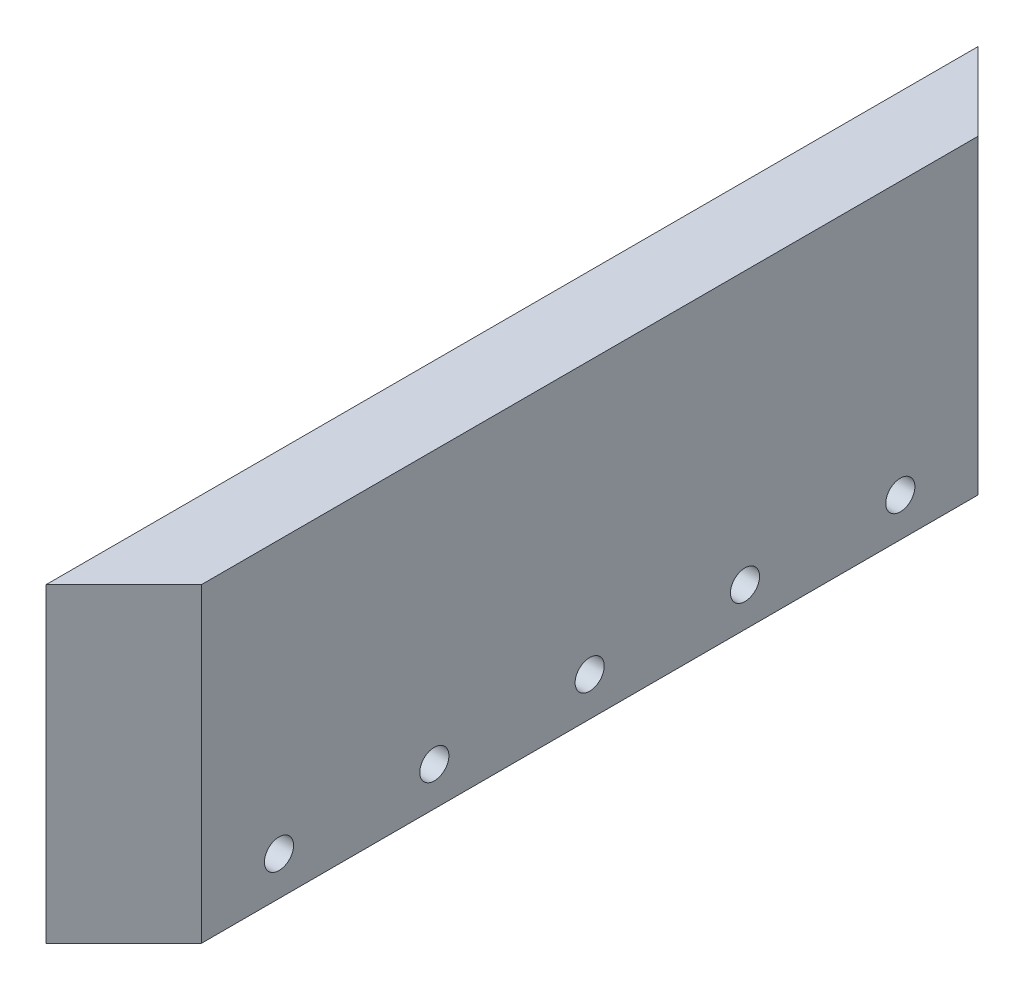
SolidWorks part; units mm, degrees
material "Mahogany"
ref_plane "Front Plane" through (0, 0, 0) normal (0, 0, 1) x (1, 0, 0)
ref_plane "Top Plane" through (0, 0, 0) normal (0, 1, 0) x (1, 0, 0)
ref_plane "Right Plane" through (0, 0, 0) normal (1, 0, 0) x (0, 0, -1)
sketch "Sketch1" plane through (0, 0, 0) normal (1, 0, 0) x (0, 0, -1)
  line L1 (-76.2, 25.4) -> (76.2, 25.4)
  line L2 (-76.2, 25.4) -> (-76.2, -25.4)
  line L3 (-76.2, -25.4) -> (76.2, -25.4)
  line L4 (76.2, 25.4) -> (76.2, -25.4)
  line L5 (-76.2, 25.4) -> (76.2, -25.4) construction
  line L6 (-76.2, -25.4) -> (76.2, 25.4) construction
  point P0 (0, 0)
  dimension "D1" = 152.4
  dimension "D2" = 50.8
extrude "Boss-Extrude1" add sketch "Sketch1" along normal blind 12.7
sketch "Sketch2" plane through (0, 25.4, 0) normal (0, 1, 0) x (1, 0, 0)
  line L0 (0, 76.2) -> (12.7, 63.5)
  line L1 (12.7, 76.2) -> (12.7, -76.2) construction
  line L2 (12.7, 63.5) -> (12.7, 76.2)
  line L3 (12.7, 76.2) -> (0, 76.2)
  line L4 (0, -76.2) -> (12.7, -63.5)
  line L5 (12.7, -63.5) -> (12.7, -76.2)
  line L6 (12.7, -76.2) -> (0, -76.2) construction
  line L7 (12.7, -76.2) -> (0, -76.2)
extrude "Cut-Extrude1" cut sketch "Sketch2" against normal through all
sketch "Sketch3" plane through (0, 25.4, 0) normal (0, 1, 0) x (1, 0, 0)
  line L0 (0, 71.7099) -> (2.2451, 73.9549)
  line L1 (0, 76.2) -> (0, -76.2) construction
  line L2 (0, 76.2) -> (12.7, 63.5) construction
  line L3 (2.2451, 73.9549) -> (0, 76.2)
  line L4 (0, 76.2) -> (0, 71.7099)
  line L5 (0, -76.2) -> (0, -71.7099)
  line L6 (0, -71.7099) -> (2.2451, -73.9549)
  line L7 (12.7, -63.5) -> (0, -76.2) construction
  line L8 (2.2451, -73.9549) -> (0, -76.2)
  dimension "D1" = 3.175
extrude "Cut-Extrude2" [suppressed] cut sketch "Sketch3" against normal through all
sketch "Sketch4" plane through (0, 0, 0) normal (-1, 0, 0) x (0, 0, 1)
  line L0 (-76.2, -992.4154) -> (-76.2, 49007.5846) construction
  line L1 (76.2, -25.4) -> (-76.2, -25.4) construction
  circle A0 centre (-50.8, -19.05) radius 2.3812
  dimension "D2" = 4.7625
  dimension "D1" = 76.2
  dimension "D3" = 6.35
  dimension "D4" = 25.4
extrude "Cut-Extrude3" cut sketch "Sketch4" against normal through all
pattern_linear "LPattern1" count 5 spacing 25.4 along (0, 0, 1) of "Cut-Extrude3"
